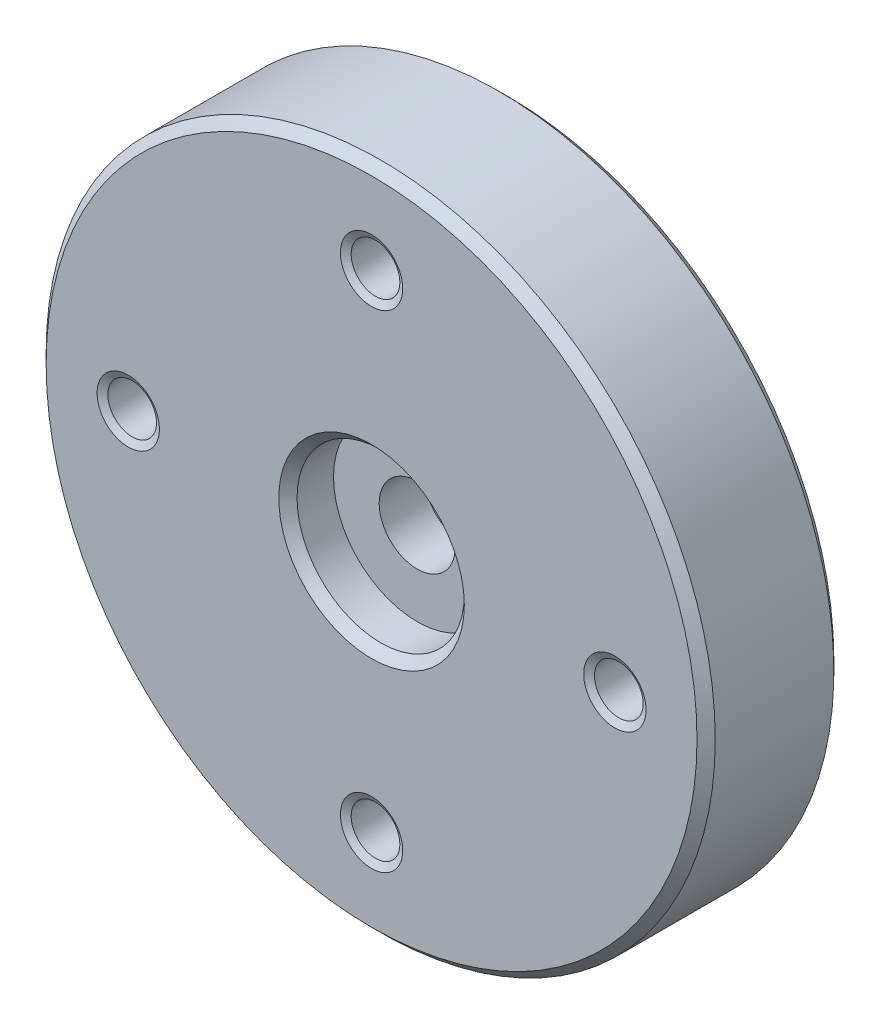
SolidWorks part; units mm, degrees
ref_plane "Front" through (0, 0, 0) normal (0, 0, 1) x (1, 0, 0)
ref_plane "Top" through (0, 0, 0) normal (0, 1, 0) x (1, 0, 0)
ref_plane "Right" through (0, 0, 0) normal (1, 0, 0) x (0, 0, -1)
sketch "Sketch1" plane through (0, 0, 0) normal (1, 0, 0) x (0, 0, -1)
  line L0 (0, 0) -> (-91.1734, 0) construction
  line L1 (3, 1.25) -> (1.5, 1.25)
  line L2 (0, 2.75) -> (0, 11)
  line L3 (0, 11) -> (4.5, 11)
  line L4 (4.5, 11) -> (4.5, 4.5)
  line L5 (4.5, 4.5) -> (6.7, 4.5)
  line L6 (6.7, 4.5) -> (6.7, 2.75)
  line L7 (6.7, 2.75) -> (3, 2.75)
  line L8 (3, 2.75) -> (3, 1.25)
  line L9 (0, 2.75) -> (1.5, 2.75)
  line L10 (1.5, 2.75) -> (1.5, 1.25)
  dimension "D1" = 2.5
  dimension "D2" = 5.5
  dimension "D3" = 1.5
  dimension "D4" = 4.5
  dimension "D5" = 22
  dimension "D6" = 9
  dimension "D7" = 5.5
  dimension "D8" = 6.7
  dimension "D9" = 3.7
revolve "Revolve1" add sketch "Sketch1" angle 360 about L0
hole_wizard "M2 Tapped Hole1" positions "Sketch3" profile "Sketch4" tap size "M2" standard "ISO" end condition up to next
sketch "Sketch3" plane through (0, 0, 0) normal (0, 0, 1) x (1, 0, 0)
  circle A0 centre (0, 0) radius 8 construction
  point P0 (0, 8)
  point P14 (8, 0)
  point P15 (0, -8)
  point P16 (-8, 0)
  point P17 (0, 0)
  dimension "D1" = 16
  dimension "D2" = 4
sketch "Sketch4" plane through (0, 8, 0) normal (1, 0, 0) x (0, -1, 0)
  line L0 (0, 0) -> (0, 4.5)
  line L1 (0, 4.5) -> (1.025, 4.5)
  line L2 (0.8, 4.3701) -> (0.8, 0.1299)
  line L3 (0.8, 0.1299) -> (1.025, 0)
  line L5 (1.025, 0) -> (0, 0)
  line L6 (-0.8, 0.1299) -> (-1.025, 0) construction
  line L7 (1.025, 4.5) -> (0.8, 4.3701)
  line L8 (-1.025, 4.5) -> (-0.8, 4.3701) construction
  line L11 (0, -6.35) -> (0, 107.95) construction
  dimension "Thru Tap Drill Dia." = 1.6
  dimension "Thru Tap Drill Depth" = 4.5
  dimension "Near C'Sink Dia." = 2.05
  dimension "Near C'Sink Angle" = 120
  dimension "Far C'Sink Dia." = 2.05
  dimension "Far C'Sink Angle" = 120
cosmetic thread "Hole Thread1" parameters "D2"=2
cosmetic thread "Hole Thread2" parameters "D2"=2
cosmetic thread "Hole Thread3" parameters "D2"=2
cosmetic thread "Hole Thread4" parameters "D2"=2
chamfer "Chamfer1" distance 0.3 angle 45 4 edges at (-11, 0, -4.5) (-11, 0, 0) (-4.5, 0, -6.7) (-2.75, 0, 0)
